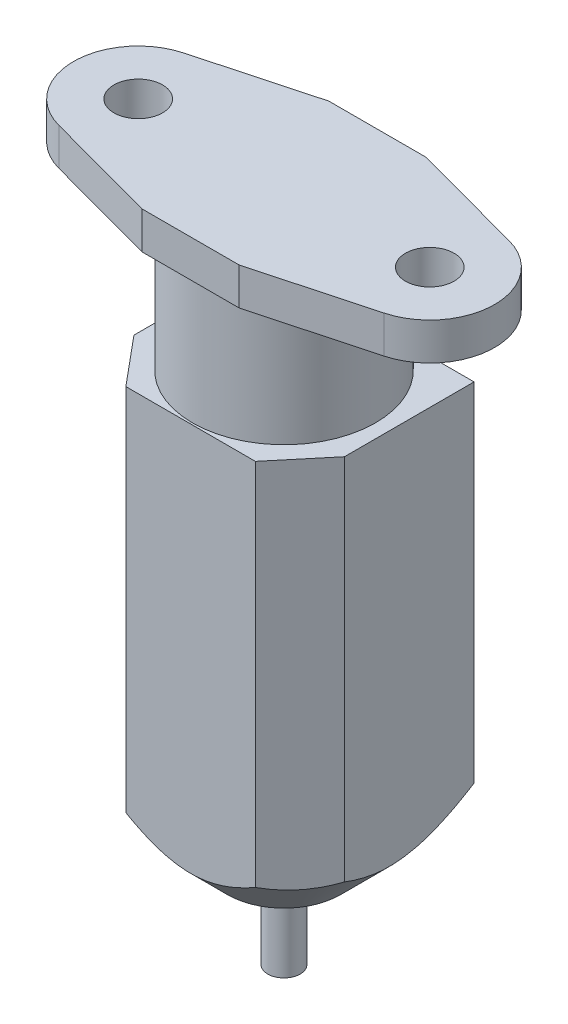
SolidWorks part; units mm, degrees
ref_plane "Front Plane" through (0, 0, 0) normal (0, 0, 1) x (1, 0, 0)
ref_plane "Top Plane" through (0, 0, 0) normal (0, 1, 0) x (1, 0, 0)
ref_plane "Right Plane" through (0, 0, 0) normal (1, 0, 0) x (0, 0, -1)
sketch "Sketch1" plane through (0, 0, 0) normal (0, 1, 0) x (1, 0, 0)
  line L0 (0, 0) -> (0, 5.765) construction
  line L1 (0, 0) -> (9, 0) construction
  line L2 (-3, 5.765) -> (3, 5.765)
  line L3 (3, 5.765) -> (10.0436, 3.8615)
  line L4 (-3, -5.765) -> (3, -5.765)
  line L5 (3, -5.765) -> (10.0436, -3.8615)
  line L6 (-3, 5.765) -> (-10.0436, 3.8615)
  line L7 (-3, -5.765) -> (-10.0436, -3.8615)
  circle A0 centre (9, 0) radius 1.5
  arc A1 (10.0436, 3.8615) -> (10.0436, -3.8615) centre (9, 0) cw
  arc A2 (-10.0436, 3.8615) -> (-10.0436, -3.8615) centre (-9, 0) ccw
  circle A3 centre (-9, 0) radius 1.5
  point P4 (0, 0)
  point P9 (0, 0)
  point P10 (16.9221, 0)
  point P11 (10.343, 3.9013)
  point P19 (0, -5.765)
  dimension "D3" = 3
  dimension "D6" = 4
  dimension "D1" = 11.53
  dimension "D4" = 9
  dimension "D5" = 6
extrude "Boss-Extrude1" add sketch "Sketch1" against normal blind 2.3
sketch "Sketch2" plane through (0, -2.3, 0) normal (0, -1, 0) x (1, 0, 0)
  circle A0 centre (0, 0) radius 5.65
  dimension "D1" = 11.3
extrude "Boss-Extrude2" add sketch "Sketch2" along normal blind 7.7
sketch "Sketch3" plane through (0, -10, 0) normal (0, -1, 0) x (1, 0, 0)
  line L0 (-4, 5.765) -> (4, 5.765)
  line L1 (-3, 5.765) -> (3, 5.765) construction
  line L2 (4, 5.765) -> (6.5, 2.765)
  line L3 (6.5, 2.765) -> (6.5, -5.235)
  line L4 (6.5, -5.235) -> (-6.5, -5.235)
  line L5 (0, 5.765) -> (0, 0) construction
  line L6 (0, 0) -> (0, -5.235) construction
  line L7 (-6.5, 2.765) -> (-6.5, -5.235)
  line L8 (-4, 5.765) -> (-6.5, 2.765)
  dimension "D1" = 13
  dimension "D2" = 11
  dimension "D3" = 8
  dimension "D4" = 3
extrude "Boss-Extrude3" add sketch "Sketch3" along normal blind 26.3
sketch "Sketch4" plane through (0, 0, 0) normal (0, 0, 1) x (1, 0, 0)
  line L0 (0, -36.3) -> (0, 0) construction
  line L1 (4, -36.3) -> (-4, -36.3) construction
  line L2 (3.5, -36.3) -> (10, -29.8)
  line L3 (10, -29.8) -> (10, -36.3)
  line L4 (10, -36.3) -> (3.5, -36.3)
  point P7 (0, 0)
  dimension "D1" = 7
  dimension "D2" = 45
  dimension "D3" = 20
revolve "Cut-Revolve1" cut sketch "Sketch4" angle 360 about L0
sketch "Sketch5" plane through (0, -36.3, 0) normal (0, -1, 0) x (1, 0, 0)
  circle A0 centre (0, 0) radius 1
  dimension "D1" = 2
extrude "Boss-Extrude4" add sketch "Sketch5" along normal blind 5.5
